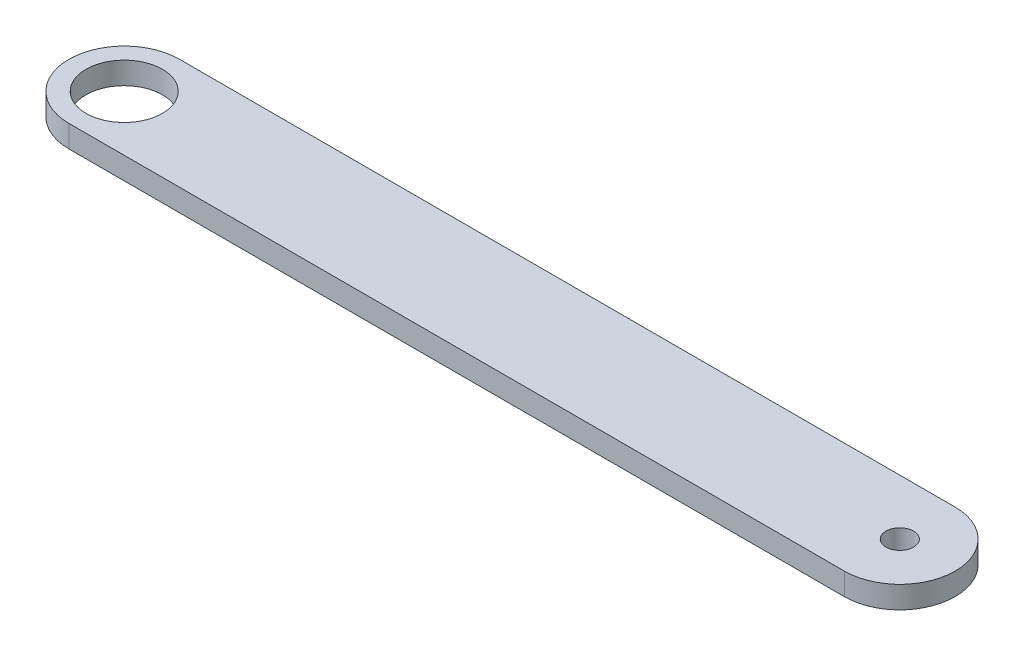
SolidWorks part; units mm, degrees
ref_plane "Front Plane" through (0, 0, 0) normal (0, 0, 1) x (1, 0, 0)
ref_plane "Top Plane" through (0, 0, 0) normal (0, 1, 0) x (1, 0, 0)
ref_plane "Right Plane" through (0, 0, 0) normal (1, 0, 0) x (0, 0, -1)
sketch "Sketch1" plane through (0, 0, 0) normal (0, 1, 0) x (1, 0, 0)
  line L0 (0, 10) -> (140, 10)
  line L1 (0, -10) -> (140, -10)
  circle A0 centre (0, 0) radius 6.9
  circle A1 centre (0, 0) radius 10
  circle A2 centre (140, 0) radius 2.5
  circle A4 centre (140, 0) radius 10
  dimension "D1" = 13.8
  dimension "D2" = 20
  dimension "D3" = 5
  dimension "D4" = 140
extrude "Boss-Extrude1" add sketch "Sketch1" along normal blind 4 contours A4 L0 A1 L1 | A1 A0 | A4 A2 region at (70, 0, 0) region at (6.8711, 0, -6.8711) region at (146.8711, 0, -6.8711)
equation "\"armLen\"= 140"
equation "\"D4@Sketch1\"=\"armLen\""
